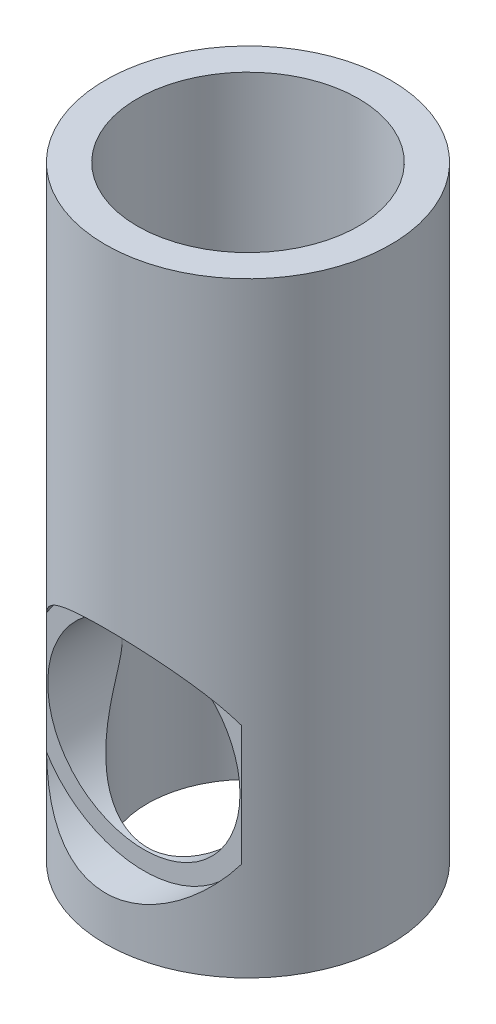
SolidWorks part; units mm, degrees
material "PTFE (general)"
ref_plane "Front Plane" through (0, 0, 0) normal (0, 0, 1) x (1, 0, 0)
ref_plane "Top Plane" through (0, 0, 0) normal (0, 1, 0) x (1, 0, 0)
ref_plane "Right Plane" through (0, 0, 0) normal (1, 0, 0) x (0, 0, -1)
sketch "Sketch1" plane through (0, 0, 0) normal (0, 1, 0) x (1, 0, 0)
  circle A0 centre (0, 0) radius 8.9
  circle A1 centre (0, 0) radius 6.28
  dimension "D1" = 17.8
  dimension "D2" = 12.56
extrude "Boss-Extrude1" add sketch "Sketch1" against normal blind 19.3
sketch "Sketch2" plane through (0, 0, 0) normal (0, -1, 0) x (-1, 0, 0)
  circle A0 centre (0, 0) radius 8.9
  circle A1 centre (0, 0) radius 6.9
  dimension "D1" = 17.8
  dimension "D2" = 13.8
extrude "Boss-Extrude2" add sketch "Sketch2" against normal blind 18.5
sketch "Sketch3" plane through (0, 0, 0) normal (0, 0, 1) x (1, 0, 0)
  line L1 (6.28, 0) -> (-6.28, 0) construction
  circle A0 centre (0, -9.4) radius 7.15
  dimension "D1" = 14.3
  dimension "D2" = 9.4
extrude "Cut-Extrude5" cut sketch "Sketch3" along normal through all from offset 6.5
sketch "Sketch6" plane through (0, 0, 6.5) normal (0, 0, 1) x (1, 0, 0)
  circle A0 centre (0, -9.4) radius 6
  dimension "D1" = 12
extrude "Cut-Extrude6" cut sketch "Sketch6" against normal blind 7 and the other way through all
